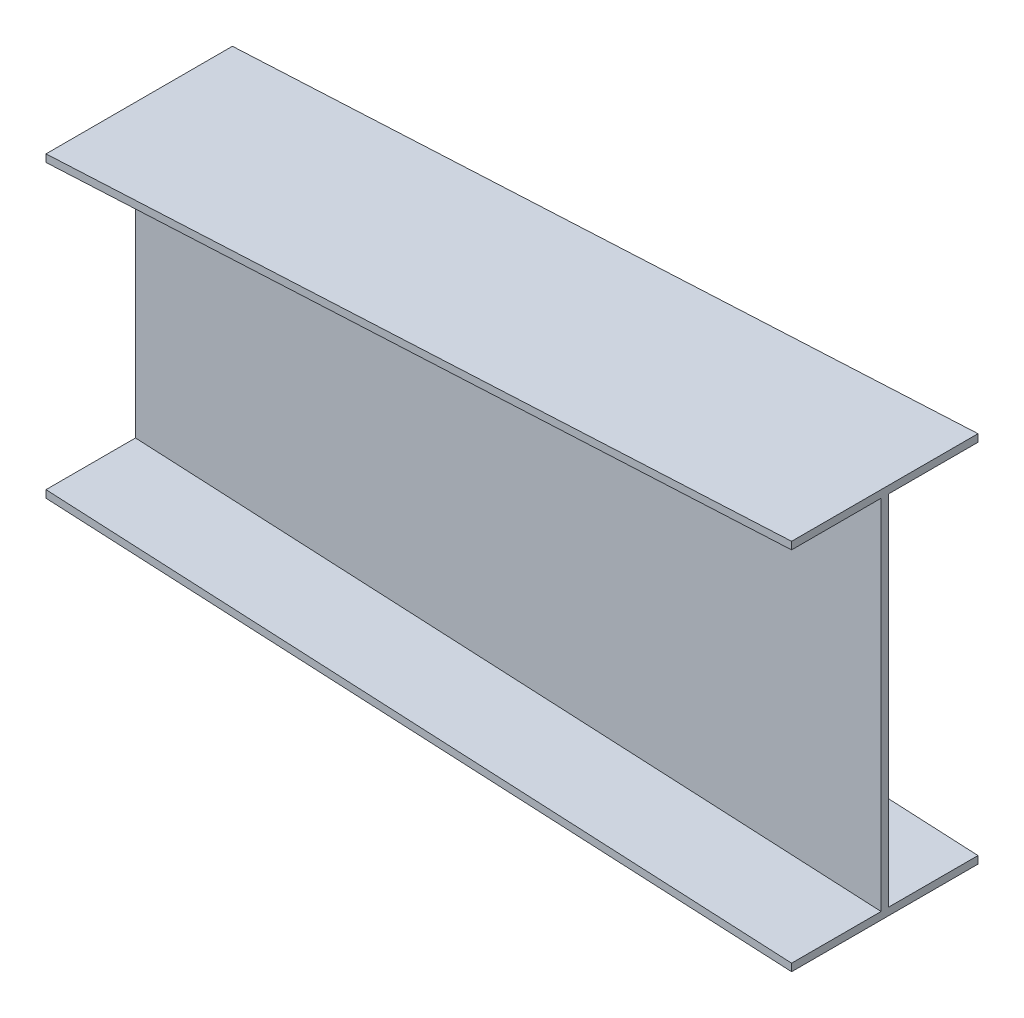
SolidWorks part; units mm, degrees
ref_plane "Front Plane" through (0, 0, 0) normal (0, 0, 1) x (1, 0, 0)
ref_plane "Top Plane" through (0, 0, 0) normal (0, 1, 0) x (1, 0, 0)
ref_plane "Right Plane" through (0, 0, 0) normal (1, 0, 0) x (0, 0, -1)
sketch "Sketch1" plane through (0, 0, 0) normal (1, 0, 0) x (0, 0, -1)
  line L1 (-130, 200) -> (120, 200)
  line L2 (-130, 200) -> (-130, 190)
  line L4 (120, 200) -> (120, 190)
  line L6 (-130, -190) -> (-130, -200)
  line L7 (-130, -200) -> (120, -200)
  line L8 (120, -190) -> (120, -200)
  line L15 (-130, -190) -> (-10, -190)
  line L16 (-5, 190) -> (-5, -790) construction
  line L18 (-130, 190) -> (-10, 190)
  line L19 (0, 0) -> (192.2403, 0) construction
  line L21 (-10, 190) -> (-10, -190)
  line L23 (0, 190) -> (0, -190)
  line L27 (0, 190) -> (120, 190)
  line L28 (0, -190) -> (120, -190)
  dimension "D1" = 250
  dimension "D2" = 10
  dimension "D3" = 400
  dimension "D4" = 10
ref_plane "Plane2" through (1000, 0, 0) normal (1, 0, 0) x (0, 0, -1)
sketch "Sketch4" plane through (1000, 0, -1000) normal (-1, 0, 0) x (0, 0, 1)
  line L1 (880, 250) -> (1130, 250)
  line L2 (880, 250) -> (880, 240)
  line L4 (1130, 250) -> (1130, 240)
  line L6 (880, -240) -> (880, -250)
  line L7 (880, -250) -> (1130, -250)
  line L8 (1130, -240) -> (1130, -250)
  line L15 (880, -240) -> (1000, -240)
  line L16 (1005, 390) -> (1005, -390) construction
  line L18 (880, 240) -> (1000, 240)
  line L19 (1010, -240) -> (1130, -240)
  line L21 (1000, 240) -> (1000, -240)
  line L23 (1010, 240) -> (1010, -240)
  line L24 (1010, 240) -> (1130, 240)
  line L26 (1010, 190) -> (1010, -190) construction
  line L27 (1000, 0) -> (820.2065, 0) construction
  dimension "D1" = 250
  dimension "D2" = 10
  dimension "D3" = 500
  dimension "D4" = 10
loft "Loft4" add profiles "Sketch1", "Sketch4" connector at (0, 190, 10) connector at (1000, 240, 10)
